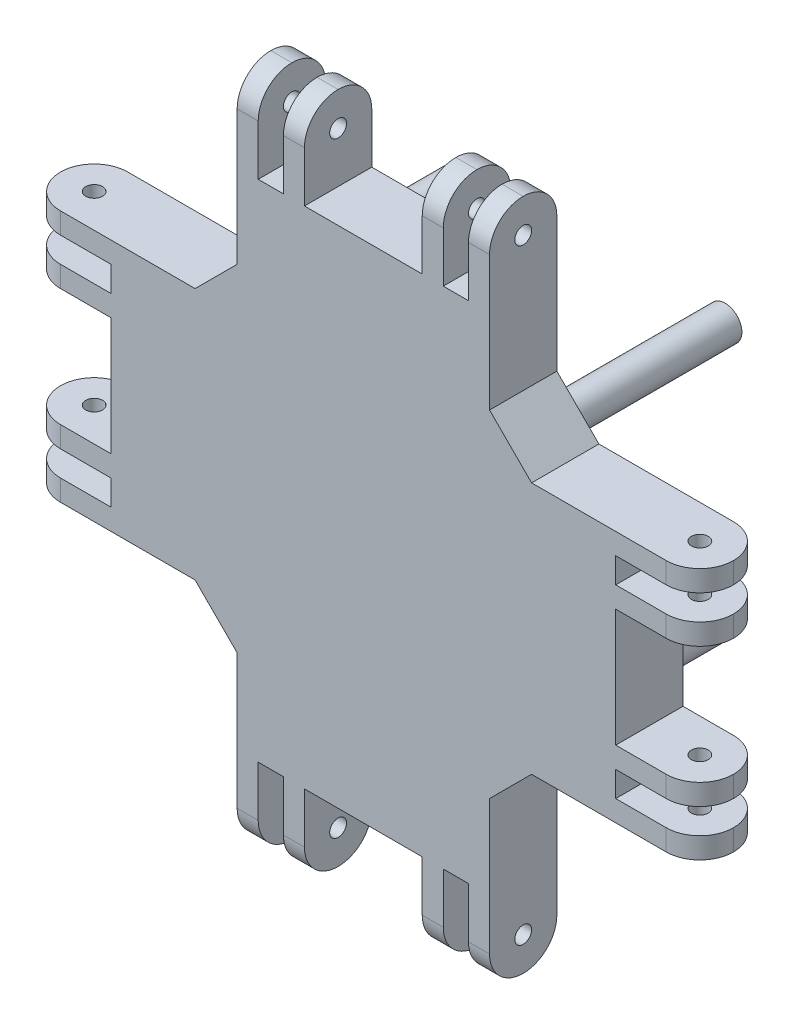
SolidWorks part; units mm, degrees
material "Thornel Mat VMA"
ref_plane "Front Plane" through (0, 0, 0) normal (0, 0, 1) x (1, 0, 0)
ref_plane "Top Plane" through (0, 0, 0) normal (0, 1, 0) x (1, 0, 0)
ref_plane "Right Plane" through (0, 0, 0) normal (1, 0, 0) x (0, 0, -1)
ref_plane "Plane1" through (0, 0, 150) normal (0, 0, 1) x (1, 0, 0)
sketch "Sketch2" plane through (0, 0, 150) normal (0, 0, 1) x (1, 0, 0)
  line L0 (-75, 200) -> (-75, 100)
  line L1 (-200, 200) -> (200, 200) construction
  line L2 (-200, 200) -> (-200, -200) construction
  line L3 (-200, -200) -> (200, -200) construction
  line L4 (200, 200) -> (200, -200) construction
  line L5 (-200, 200) -> (200, -200) construction
  line L6 (-200, -200) -> (200, 200) construction
  line L7 (35, 200) -> (47.5, 200)
  line L8 (47.5, 200) -> (47.5, 150)
  line L9 (-35, 200) -> (-35, 150)
  line L10 (-35, 150) -> (35, 150)
  line L11 (35, 150) -> (35, 200)
  line L12 (47.5, 150) -> (62.5, 150)
  line L13 (-75, 200) -> (-62.5, 200)
  line L14 (-62.5, 200) -> (-62.5, 150)
  line L15 (-62.5, 150) -> (-47.5, 150)
  line L16 (-47.5, 150) -> (-47.5, 200)
  line L17 (-47.5, 200) -> (-35, 200)
  line L18 (62.5, 150) -> (62.5, 200)
  line L19 (62.5, 200) -> (75, 200)
  line L20 (75, 200) -> (75, 100)
  line L21 (100, 75) -> (200, 75)
  line L22 (200, 75) -> (200, 62.5)
  line L23 (200, 62.5) -> (150, 62.5)
  line L24 (150, 62.5) -> (150, 47.5)
  line L25 (150, 47.5) -> (200, 47.5)
  line L26 (200, 47.5) -> (200, 35)
  line L27 (200, 35) -> (150, 35)
  line L28 (150, 35) -> (150, -35)
  line L29 (150, -35) -> (200, -35)
  line L30 (200, -35) -> (200, -47.5)
  line L31 (200, -47.5) -> (150, -47.5)
  line L32 (150, -47.5) -> (150, -62.5)
  line L33 (150, -62.5) -> (200, -62.5)
  line L34 (200, -62.5) -> (200, -75)
  line L35 (200, -75) -> (100, -75)
  line L36 (100, -75) -> (75, -100)
  line L37 (75, -100) -> (75, -200)
  line L38 (75, -200) -> (62.5, -200)
  line L39 (62.5, -200) -> (62.5, -150)
  line L40 (62.5, -150) -> (47.5, -150)
  line L41 (47.5, -150) -> (47.5, -200)
  line L42 (47.5, -200) -> (35, -200)
  line L43 (35, -200) -> (35, -150)
  line L44 (35, -150) -> (-35, -150)
  line L45 (-35, -150) -> (-35, -200)
  line L46 (-35, -200) -> (-47.5, -200)
  line L47 (-47.5, -200) -> (-47.5, -150)
  line L48 (-47.5, -150) -> (-62.5, -150)
  line L49 (-62.5, -150) -> (-62.5, -200)
  line L50 (-62.5, -200) -> (-75, -200)
  line L51 (-75, -200) -> (-75, -100)
  line L52 (-75, -100) -> (-100, -75)
  line L53 (-100, -75) -> (-200, -75)
  line L54 (-200, -75) -> (-200, -62.5)
  line L55 (-200, -62.5) -> (-150, -62.5)
  line L56 (-150, -62.5) -> (-150, -47.5)
  line L57 (-150, -47.5) -> (-200, -47.5)
  line L58 (-200, -47.5) -> (-200, -35)
  line L59 (-200, -35) -> (-150, -35)
  line L60 (-150, -35) -> (-150, 35)
  line L61 (-150, 35) -> (-200, 35)
  line L62 (-200, 35) -> (-200, 47.5)
  line L63 (-200, 47.5) -> (-150, 47.5)
  line L64 (-150, 47.5) -> (-150, 62.5)
  line L65 (-150, 62.5) -> (-200, 62.5)
  line L66 (-200, 62.5) -> (-200, 75)
  line L67 (-200, 75) -> (-100, 75)
  line L68 (-100, 75) -> (-75, 100)
  line L69 (75, 100) -> (100, 75)
  point P0 (0, 0)
  point P8 (0, 150)
  point P72 (150, 0)
  point P74 (0, -150)
  point P75 (-150, 0)
  dimension "D1" = 400
  dimension "D2" = 400
  dimension "D3" = 12.5
  dimension "D4" = 40
  dimension "D5" = 12.5
  dimension "D6" = 70
  dimension "D7" = 50
  dimension "D8" = 50
  dimension "D9" = 100
  dimension "D10" = 50
  dimension "D11" = 12.5
  dimension "D12" = 12.5
  dimension "D13" = 15
  dimension "D14" = 100
  dimension "D15" = 70
  dimension "D16" = 12.5
  dimension "D17" = 12.5
  dimension "D18" = 15
  dimension "D19" = 12.5
  dimension "D20" = 12.5
  dimension "D21" = 15
  dimension "D22" = 50
  dimension "D23" = 50
  dimension "D24" = 50
  dimension "D25" = 100
  dimension "D26" = 12.5
  dimension "D27" = 12.5
  dimension "D28" = 15
  dimension "D29" = 12.5
  dimension "D30" = 12.5
  dimension "D31" = 15
  dimension "D32" = 70
  dimension "D33" = 100
  dimension "D34" = 100
  dimension "D35" = 12.5
  dimension "D36" = 12.5
  dimension "D37" = 12.5
  dimension "D38" = 12.5
  dimension "D39" = 15
  dimension "D40" = 15
  dimension "D41" = 70
  dimension "D42" = 100
  dimension "D43" = 100
  dimension "D44" = 100
  dimension "D45" = 50
  dimension "D46" = 50
  dimension "D47" = 50
  dimension "D48" = 50
  dimension "D49" = 50
  dimension "D50" = 50
extrude "Boss-Extrude1" add sketch "Sketch2" against normal blind 40
fillet "Fillet1" radius 20 32 edges at (68.75, -200, 110) (41.25, -200, 110) (-41.25, -200, 110) (-68.75, -200, 110) (-200, -68.75, 110) (-200, -41.25, 110) (-200, 41.25, 110) (-200, 68.75, 110) (-68.75, -200, 150) (41.25, -200, 150) (-41.25, -200, 150) (68.75, -200, 150) (-200, -68.75, 150) (-200, -41.25, 150) (-200, 41.25, 150) (-200, 68.75, 150) (200, -68.75, 110) (200, -68.75, 150) (-68.75, 200, 110) (-68.75, 200, 150) (-41.25, 200, 110) (-41.25, 200, 150) (41.25, 200, 110) (41.25, 200, 150) (68.75, 200, 110) (68.75, 200, 150) (200, 68.75, 110) (200, 68.75, 150) (200, 41.25, 110) (200, 41.25, 150) (200, -41.25, 110) (200, -41.25, 150)
sketch "Sketch6" plane through (75, 0, 0) normal (1, 0, 0) x (0, 1, 0)
  circle A0 centre (180, 130) radius 5
extrude "Cut-Extrude1" cut sketch "Sketch6" against normal blind 165
sketch "Sketch7" plane through (0, 75, 0) normal (0, 1, 0) x (-1, 0, 0)
  circle A0 centre (180, 130) radius 5
extrude "Cut-Extrude2" cut sketch "Sketch7" against normal blind 165
sketch "Sketch8" plane through (-75, 0, 0) normal (-1, 0, 0) x (0, -1, 0)
  circle A0 centre (180, 130) radius 5
extrude "Cut-Extrude3" cut sketch "Sketch8" against normal blind 165
sketch "Sketch10" plane through (0, 75, 0) normal (0, 1, 0) x (-1, 0, 0)
  circle A0 centre (-180, 130) radius 5
extrude "Cut-Extrude4" cut sketch "Sketch10" against normal blind 165
sketch "Sketch11" plane through (0, 0, 110) normal (0, 0, -1) x (1, 0, 0)
  line L1 (-75, 75) -> (75, 75) construction
  line L2 (-75, 75) -> (-75, -75) construction
  line L3 (-75, -75) -> (75, -75) construction
  line L4 (75, 75) -> (75, -75) construction
  line L5 (-75, 75) -> (75, -75) construction
  line L6 (-75, -75) -> (75, 75) construction
  circle A0 centre (-75, 75) radius 10
  circle A1 centre (75, 75) radius 10
  circle A2 centre (-75, -75) radius 10
  circle A3 centre (75, -75) radius 10
  point P0 (0, 0)
  dimension "D3" = 20
  dimension "D1" = 150
  dimension "D2" = 150
extrude "Boss-Extrude2" add sketch "Sketch11" along normal blind 100
shell "Shell1" thickness 5
